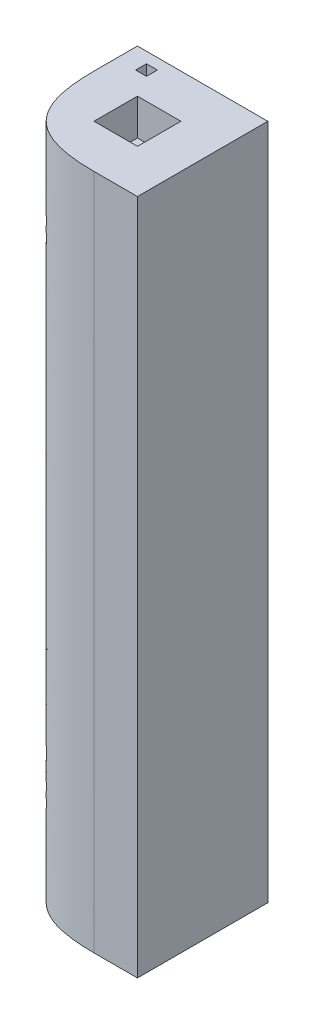
SolidWorks part; units mm, degrees
ref_plane "Front Plane" through (0, 0, 0) normal (0, 0, 1) x (1, 0, 0)
ref_plane "Top Plane" through (0, 0, 0) normal (0, 1, 0) x (1, 0, 0)
ref_plane "Right Plane" through (0, 0, 0) normal (1, 0, 0) x (0, 0, -1)
sketch "Sketch1" plane through (0, 0, 0) normal (0, 1, 0) x (1, 0, 0)
  line L1 (0, 0) -> (36, 0)
  line L2 (0, 0) -> (0, 36)
  line L3 (0, 36) -> (36, 36)
  line L4 (36, 0) -> (36, 36)
  dimension "D1" = 36
  dimension "D2" = 36
extrude "Boss-Extrude1" add sketch "Sketch1" along normal blind 186.9
fillet "Fillet1" radius 24 1 edges at (0, 93.45, 0) conic rho 0.55
sketch "Sketch2" plane through (0, 0, 0) normal (0, -1, 0) x (1, 0, 0)
  line L0 (36, -36) -> (0, -36) construction
  line L2 (36, 0) -> (36, -36) construction
  line L3 (24, 0) -> (36, 0) construction
  circle A0 centre (18, -18) radius 2
  dimension "D1" = 4
  dimension "D2" = 18
  dimension "D3" = 18
extrude "Cut-Extrude1" cut sketch "Sketch2" against normal blind 5
sketch "Sketch3" plane through (0, 0, 0) normal (0, -1, 0) x (1, 0, 0)
  line L0 (36, 0) -> (36, -36) construction
  line L1 (26, -5) -> (31, -5)
  line L2 (26, -5) -> (26, -26)
  line L3 (26, -31) -> (31, -31)
  line L4 (31, -5) -> (31, -31)
  line L5 (24, 0) -> (36, 0) construction
  line L6 (36, -36) -> (0, -36) construction
  line L7 (0, -36) -> (0, -24) construction
  line L8 (5, -31) -> (26, -31)
  line L9 (5, -31) -> (5, -26)
  line L10 (5, -26) -> (26, -26)
  line L13 (9, -9) -> (14, -9)
  line L14 (9, -9) -> (9, -14)
  line L15 (9, -14) -> (14, -14)
  line L16 (14, -9) -> (14, -14)
  dimension "D7" = 5
  dimension "D8" = 5
  dimension "D9" = 12
  dimension "D1" = 5
  dimension "D2" = 5
  dimension "D3" = 5
  dimension "D4" = 5
  dimension "D5" = 5
  dimension "D6" = 5
  dimension "D10" = 12
  dimension "D11" = 9
  dimension "D12" = 9
extrude "Boss-Extrude2" add sketch "Sketch3" along normal blind 4
sketch "Sketch4" plane through (0, 0, -36) normal (0, 0, -1) x (-1, 0, 0)
  line L0 (0, 186.9) -> (0, 0) construction
  line L1 (-10, 182.9) -> (-4, 182.9)
  line L2 (-10, 182.9) -> (-10, 178.9)
  line L3 (-10, 178.9) -> (-4, 178.9)
  line L4 (-4, 182.9) -> (-4, 178.9)
  line L5 (-36, 186.9) -> (0, 186.9) construction
  line L6 (-36, 186.9) -> (-36, 0) construction
  line L7 (-32, 182.9) -> (-26, 182.9)
  line L8 (-32, 182.9) -> (-32, 178.9)
  line L9 (-32, 178.9) -> (-26, 178.9)
  line L10 (-26, 182.9) -> (-26, 178.9)
  line L12 (-10, 162.9) -> (-4, 162.9)
  line L13 (-10, 162.9) -> (-10, 158.9)
  line L14 (-10, 158.9) -> (-4, 158.9)
  line L15 (-4, 162.9) -> (-4, 158.9)
  dimension "D1" = 4
  dimension "D2" = 4
  dimension "D3" = 4
  dimension "D4" = 6
  dimension "D5" = 6
  dimension "D6" = 4
  dimension "D7" = 4
  dimension "D8" = 4
  dimension "D9" = 16
  dimension "D10" = 4
extrude "Cut-Extrude2" cut sketch "Sketch4" against normal blind 9
sketch "Sketch5" plane through (0, 186.9, 0) normal (0, 1, 0) x (1, 0, 0)
  line L0 (0, 36) -> (0, 24) construction
  line L1 (5.5, 33) -> (8.5, 33)
  line L2 (5.5, 33) -> (5.5, 30)
  line L3 (5.5, 30) -> (8.5, 30)
  line L4 (8.5, 33) -> (8.5, 30)
  line L5 (36, 36) -> (0, 36) construction
  line L6 (24, 0) -> (36, 0) construction
  line L7 (12, 12) -> (24, 12)
  line L8 (12, 12) -> (12, 24)
  line L9 (12, 24) -> (24, 24)
  line L10 (24, 12) -> (24, 24)
  dimension "D1" = 3
  dimension "D2" = 3
  dimension "D3" = 5.5
  dimension "D4" = 3
  dimension "D5" = 12
  dimension "D6" = 12
  dimension "D7" = 12
  dimension "D8" = 12
extrude "Cut-Extrude3" cut sketch "Sketch5" against normal blind 10
